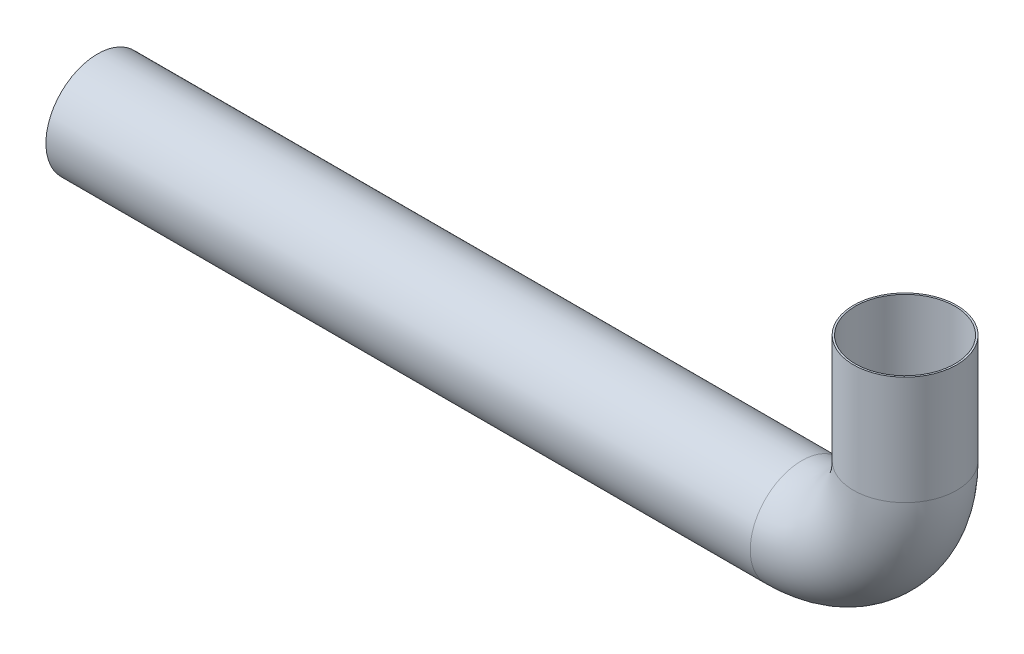
SolidWorks part; units mm, degrees
ref_plane "Plano frontal" through (0, 0, 0) normal (0, 0, 1) x (1, 0, 0)
ref_plane "Plano superior" through (0, 0, 0) normal (0, 1, 0) x (1, 0, 0)
ref_plane "Plano direito" through (0, 0, 0) normal (1, 0, 0) x (0, 0, -1)
sketch3d "3DSketch1"
  line L0 (-30291.578, -16257.8596, 40521.7032) -> (-29599.189, -16257.8596, 40521.7032) construction
  line L1 (-30137.4493, -16257.8596, 40521.7032) -> (-30341.5521, -16257.8596, 40521.7032) construction
  line L2 (-29599.189, -16130.8915, 40521.7032) -> (-29599.189, -16257.8596, 40521.7032) construction
  line L3 (-30068.5409, -16257.8596, 40521.7032) -> (-29659.189, -16257.8596, 40521.7032)
  line L4 (-29599.189, -16197.8596, 40521.7032) -> (-29599.189, -16134.6862, 40521.7032)
  circle A0 centre (-29599.189, -16130.8915, 40521.7032) radius 30.226 construction
  arc A1 (-29599.189, -16197.8596, 40521.7032) -> (-29659.189, -16257.8596, 40521.7032) centre (-29659.189, -16197.8596, 40521.7032) ccw
  point P10 (-29598.8132, -16100.6679, 40521.7032)
  point P12 (-29599.189, -16257.8596, 40521.7032)
  point P14 (-29659.189, -16197.8596, 40461.7032)
  point P15 (-29599.189, -16134.6862, 40521.7032)
  dimension "D1" = 60
sweep "Sweep-Thin1" add path "3DSketch1" circular profile diameter 60 parameters "D1"=1, "D3"=60
